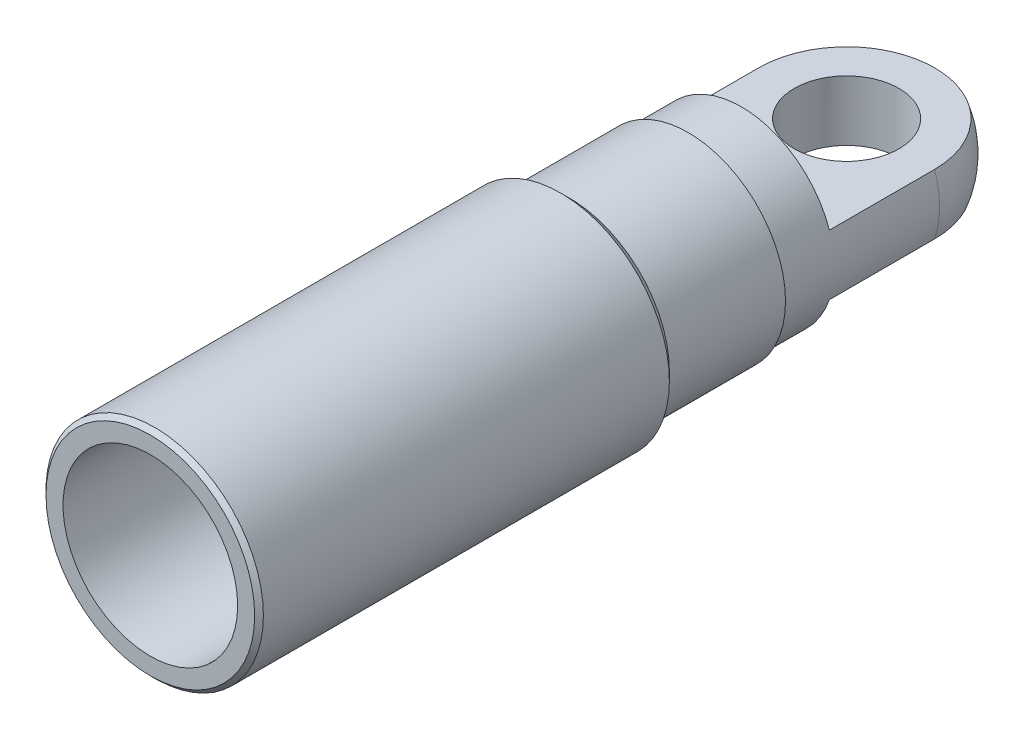
SolidWorks part; units mm, degrees
material "2024-T3"
ref_plane "Front Plane" through (0, 0, 0) normal (0, 0, 1) x (1, 0, 0)
ref_plane "Top Plane" through (0, 0, 0) normal (0, 1, 0) x (1, 0, 0)
ref_plane "Right Plane" through (0, 0, 0) normal (1, 0, 0) x (0, 0, -1)
sketch "Sketch1" plane through (0, 0, 0) normal (0, 0, 1) x (1, 0, 0)
  circle A0 centre (0, 0) radius 5.325
  dimension "D1" = 10.65
extrude "Boss-Extrude1" add sketch "Sketch1" along normal blind 14.4
sketch "Sketch2" plane through (0, 0, 14.4) normal (0, 0, 1) x (1, 0, 0)
  circle A0 centre (0, 0) radius 5.575
  dimension "D1" = 11.15
extrude "Boss-Extrude2" add sketch "Sketch2" along normal blind 6.8
sketch "Sketch3" plane through (0, 0, 21.2) normal (0, 0, 1) x (1, 0, 0)
  circle A0 centre (0, 0) radius 6.225
  dimension "D1" = 12.45
extrude "Boss-Extrude3" add sketch "Sketch3" along normal blind 24
fillet "Fillet1" radius 5.325 1 edges at (5.325, 0, 0)
sketch "Sketch4" plane through (0, 0, 0) normal (1, 0, 0) x (0, 0, -1)
  line L0 (0, 0) -> (-92.0537, 0) construction
  line L1 (2.2252, 1.725) -> (-11.35, 1.725)
  line L2 (2.2252, -1.725) -> (-11.35, -1.725)
  line L3 (-11.35, 1.725) -> (-11.35, 16.3155)
  line L4 (-11.35, 16.3155) -> (23.6587, 16.3155)
  line L5 (23.6587, 16.3155) -> (23.6587, -14.3177)
  line L6 (23.6587, -14.3177) -> (-11.35, -14.3177)
  line L7 (-11.35, -14.3177) -> (-11.35, -1.725)
  line L8 (2.2252, 1.725) -> (2.2252, -1.725)
  dimension "D1" = 11.35
  dimension "D2" = 3.45
extrude "Cut-Extrude1" cut sketch "Sketch4" against normal blind 48 and the other way blind 48
sketch "Sketch5" plane through (0, 1.725, 0) normal (0, 1, 0) x (1, 0, 0)
  line L0 (5.0379, -11.35) -> (-5.0379, -11.35) construction
  circle A0 centre (0, -5.325) radius 3
  dimension "D1" = 6
  dimension "D2" = 6.025
extrude "Cut-Extrude2" cut sketch "Sketch5" against normal blind 48
chamfer "Chamfer1" distance 0.5 angle 45 1 edges at (6.225, 0, 21.2)
sketch "Sketch6" plane through (0, 0, 45.2) normal (0, 0, 1) x (1, 0, 0)
  circle A0 centre (0, 0) radius 5
  dimension "D1" = 10
extrude "Cut-Extrude3" cut sketch "Sketch6" against normal blind 32.5
chamfer "Chamfer2" distance 0.25 angle 45 1 edges at (6.225, 0, 45.2)
